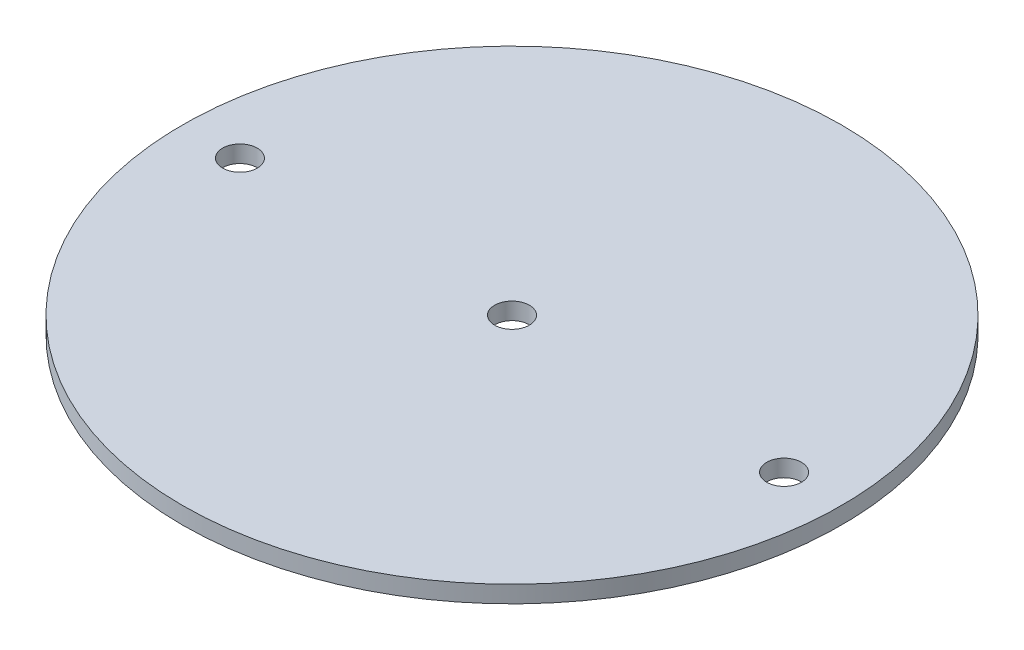
SolidWorks part; units mm, degrees
ref_plane "Front Plane" through (0, 0, 0) normal (0, 0, 1) x (1, 0, 0)
ref_plane "Top Plane" through (0, 0, 0) normal (0, 1, 0) x (1, 0, 0)
ref_plane "Right Plane" through (0, 0, 0) normal (1, 0, 0) x (0, 0, -1)
sketch "Sketch2" plane through (0, 0, 0) normal (0, 1, 0) x (1, 0, 0)
  line L0 (-50.8, 0) -> (50.8, 0) construction
  circle A0 centre (0, 0) radius 61.5315
  circle A1 centre (-50.8, 0) radius 3.2385
  circle A2 centre (50.8, 0) radius 3.2385
  circle A3 centre (0, 0) radius 3.2385
  point P6 (0, 0)
  dimension "D1" = 123.063
  dimension "D3" = 6.477
  dimension "D4" = 6.477
  dimension "D2" = 101.6
extrude "Boss-Extrude1" add sketch "Sketch2" along normal blind 3.175
